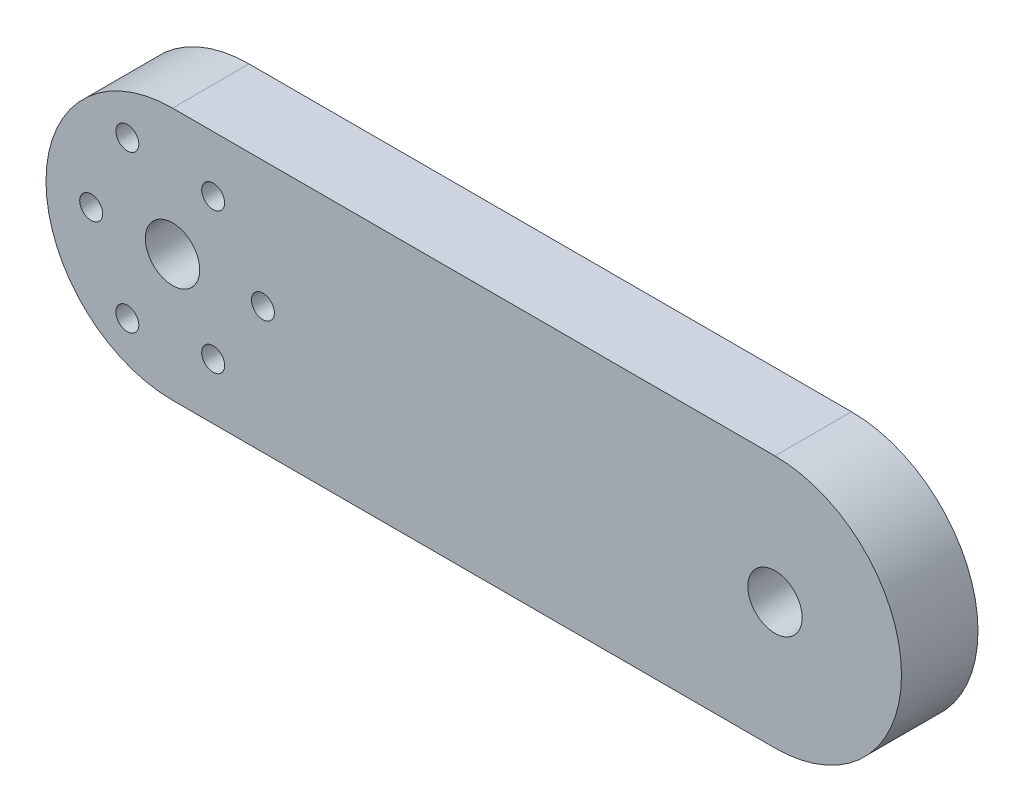
SolidWorks part; units mm, degrees
material "Alloy Steel"
ref_plane "Front Plane" through (0, 0, 0) normal (0, 0, 1) x (1, 0, 0)
ref_plane "Top Plane" through (0, 0, 0) normal (0, 1, 0) x (1, 0, 0)
ref_plane "Right Plane" through (0, 0, 0) normal (1, 0, 0) x (0, 0, -1)
sketch "Sketch1" plane through (0, 0, 0) normal (0, 0, 1) x (1, 0, 0)
  line L0 (0, 0) -> (100, 0) construction
  line L1 (0, 21) -> (100, 21)
  line L2 (0, -21) -> (100, -21)
  arc A1 (0, 21) -> (0, -21) centre (0, 0) ccw
  arc A2 (100, -21) -> (100, 21) centre (100, 0) ccw
  circle A3 centre (100, 0) radius 4.5085
  circle A4 centre (0, 0) radius 15 construction
  circle A5 centre (15, 0) radius 1.905
  circle A6 centre (-7.5, -12.9904) radius 1.905
  circle A7 centre (-7.5, 12.9904) radius 1.905
  circle A8 centre (0, 0) radius 4.5085
  circle A9 centre (0, 0) radius 13.5 construction
  circle A10 centre (-13.5, 0) radius 1.905
  circle A11 centre (6.75, 11.6913) radius 1.905
  circle A12 centre (6.75, -11.6913) radius 1.905
  point P3 (50, 0)
  point P20 (0, 0)
  point P29 (0, 0)
  dimension "D1" = 9.017
  dimension "D2" = 30
  dimension "D3" = 3.81
  dimension "D5" = 9.017
  dimension "D6" = 27
  dimension "D7" = 3.81
  dimension "D4" = 3
  dimension "D8" = 3
extrude "Boss-Extrude2" add sketch "Sketch1" along normal blind 12.7
